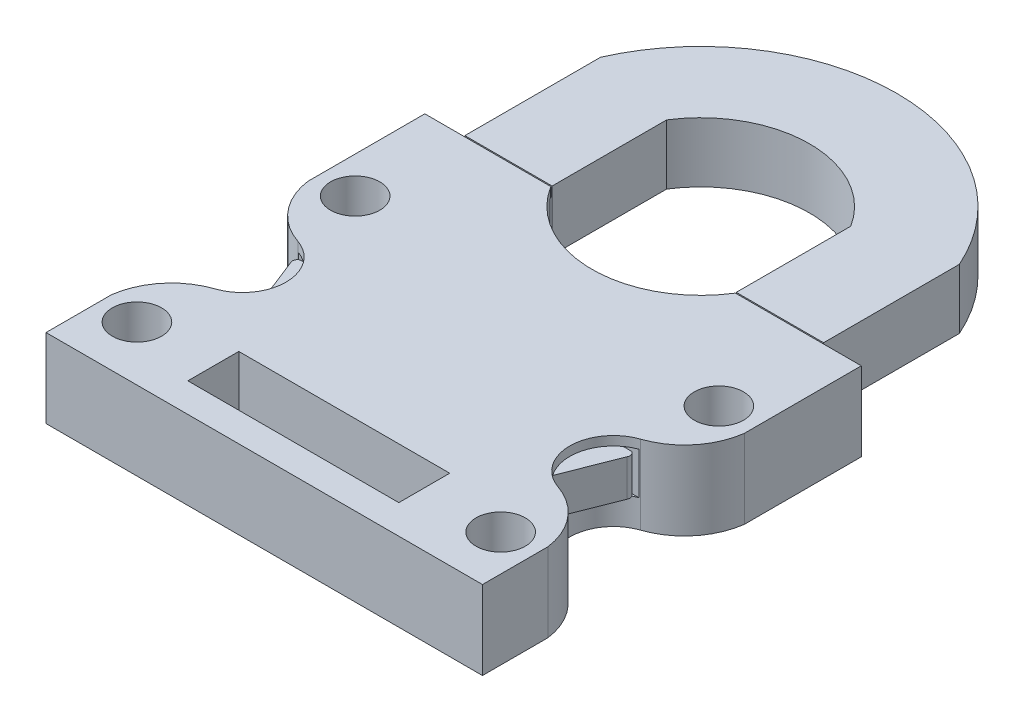
SolidWorks part; units mm, degrees
ref_plane "Front Plane" through (0, 0, 0) normal (0, 0, 1) x (1, 0, 0)
ref_plane "Top Plane" through (0, 0, 0) normal (0, 1, 0) x (1, 0, 0)
ref_plane "Right Plane" through (0, 0, 0) normal (1, 0, 0) x (0, 0, -1)
sketch "Sketch1" plane through (0, 0, 0) normal (0, 1, 0) x (1, 0, 0)
  line L0 (-38.1, -28.575) -> (38.1, -28.575)
  line L1 (31.75, -19.05) -> (-31.75, -19.05) construction
  line L2 (31.75, -19.05) -> (31.75, 19.05) construction
  line L3 (31.75, 19.05) -> (-31.75, 19.05) construction
  line L4 (-31.75, -19.05) -> (-31.75, 19.05) construction
  line L5 (31.75, -19.05) -> (-31.75, 19.05) construction
  line L6 (31.75, 19.05) -> (-31.75, -19.05) construction
  line L11 (38.1, -28.575) -> (38.1, 37.5615)
  line L13 (-38.1, 37.5615) -> (-38.1, -28.575)
  line L14 (-15.875, 37.5615) -> (-38.1, 37.5615)
  line L15 (0, -28.575) -> (0, 28.829) construction
  line L21 (15.875, 37.5615) -> (38.1, 37.5615)
  line L22 (0, 47.625) -> (0, -28.575) construction
  line L29 (0, 28.829) -> (0, -28.575) construction
  circle A0 centre (-31.75, 19.05) radius 2.75
  circle A1 centre (31.75, 19.05) radius 2.75
  circle A2 centre (31.75, -19.05) radius 2.75
  circle A3 centre (-31.75, -19.05) radius 2.75
  arc A4 (-15.875, 37.5615) -> (15.875, 37.5615) centre (0, 47.625) ccw
  point P0 (0, 0)
  point P10 (0, 0)
  dimension "D3" = 5.5
  dimension "D8" = 37.592
  dimension "D1" = 63.5
  dimension "D2" = 38.1
  dimension "D4" = 76.2
  dimension "D5" = 9.525
  dimension "D6" = 22.225
  dimension "D7" = 76.2
  dimension "D9" = 66.1365
extrude "Boss-Extrude1" add sketch "Sketch1" along normal blind 10.6045
sketch "Sketch2" plane through (0, 10.6045, 0) normal (0, 1, 0) x (1, 0, 0)
  circle A0 centre (-31.75, 19.05) radius 4.3
  circle A1 centre (31.75, 19.05) radius 4.3
  circle A2 centre (31.75, -19.05) radius 4.3
  circle A3 centre (-31.75, -19.05) radius 4.3
  dimension "D1" = 8.6
  dimension "D2" = 8.6
  dimension "D3" = 8.6
  dimension "D4" = 8.6
extrude "Cut-Extrude1" cut sketch "Sketch2" against normal blind 7
sketch "Sketch3" plane through (0, 0, -37.5615) normal (0, 0, -1) x (-1, 0, 0)
  line L0 (15.875, 0) -> (15.875, 5.3022) construction
  line L1 (15.875, 9.017) -> (25.4, 9.017)
  line L2 (15.875, 9.017) -> (15.875, 1.5875)
  line L3 (15.875, 1.5875) -> (25.4, 1.5875)
  line L4 (25.4, 9.017) -> (25.4, 1.5875)
  line L6 (15.875, 0) -> (38.1, 0) construction
  line L7 (15.875, 10.6045) -> (38.1, 10.6045) construction
  line L8 (38.1, 10.6045) -> (38.1, 0) construction
  line L9 (15.875, 10.6045) -> (15.875, 0) construction
  dimension "D2" = 1.5875
  dimension "D3" = 1.5875
  dimension "D4" = 12.7
extrude "Cut-Extrude2" cut sketch "Sketch3" against normal blind 30.5816
mirror "Mirror1" about plane through (0, 0, 0) normal (1, 0, 0) of "Cut-Extrude2"
sketch "Sketch4" plane through (-38.1, 0, 0) normal (-1, 0, 0) x (0, 0, 1)
  line L0 (-6.9799, 9.017) -> (-37.5615, 9.017) construction
  line L5 (-14.75, 7.1045) -> (14.75, 7.1045) construction
  line L6 (-14.75, 3.6045) -> (-14.75, 10.6045) construction
  line L7 (14.75, 10.6045) -> (14.75, 3.6045) construction
  line L9 (0, 0) -> (0, 10.6045) construction
  line L10 (-37.5615, 10.6045) -> (28.575, 10.6045) construction
  line L11 (7.13, 1.5875) -> (-7.13, 1.5875)
  line L12 (7.13, 1.5875) -> (7.13, 9.017)
  line L13 (7.13, 9.017) -> (-7.13, 9.017)
  line L14 (-7.13, 1.5875) -> (-7.13, 9.017)
  line L15 (7.13, 1.5875) -> (-7.13, 9.017) construction
  line L16 (7.13, 9.017) -> (-7.13, 1.5875) construction
  line L17 (-37.5615, 5.3022) -> (-7.13, 5.3022) construction
  line L18 (-37.5615, 10.6045) -> (-37.5615, 0) construction
  point P4 (0, 5.3022)
  dimension "D1" = 7.62
ref_plane "Plane1" through (0, 5.3022, 0) normal (0, 1, 0) x (1, 0, 0)
extrude "Cut-Extrude5" cut sketch "Sketch4" against normal up to body separate body
sketch "Sketch6" plane through (0, 5.3022, 0) normal (0, 1, 0) x (1, 0, 0)
  line L0 (15.875, 33.3699) -> (15.875, 7.13)
  line L1 (15.875, 7.13) -> (15.875, 37.5615) construction
  line L2 (15.875, 7.13) -> (9.525, 7.13)
  line L3 (15.875, 7.13) -> (-15.875, 7.13) construction
  line L4 (9.525, 7.13) -> (9.525, 28.5331)
  arc A2 (-18.0203, 36.2016) -> (18.0203, 36.2016) centre (0, 47.625) ccw
  arc A3 (9.525, 28.5331) -> (15.875, 33.3699) centre (0, 47.625) ccw
  dimension "D2" = 6.35
  dimension "D1" = 2.54
extrude "Cut-Extrude6" cut sketch "Sketch6" against normal mid plane 7.4295
mirror "Mirror3" about plane through (0, 0, 0) normal (1, 0, 0) of "Cut-Extrude6"
sketch "Sketch7" plane through (0, 5.3022, 0) normal (0, 1, 0) x (1, 0, 0)
  line L0 (-38.1, 17.145) -> (-38.1, 0)
  line L3 (-38.1, 37.5615) -> (-38.1, -28.575) construction
  line L4 (-24.765, 0) -> (-38.1, 0) construction
  line L6 (-38.1, 0) -> (-24.765, 0)
  arc A2 (-38.1, 17.145) -> (-29.9352, 7.2155) centre (-26.0155, 18.7602) ccw
  arc A3 (-29.9352, 7.2155) -> (-24.765, 0) centre (-32.385, 0) cw
  dimension "D1" = 12.192
  dimension "D3" = 7.62
  dimension "D2" = 13.335
  dimension "D4" = 17.145
extrude "Cut-Extrude7" cut sketch "Sketch7" against normal mid plane 11.43
mirror "Mirror4" about plane through (0, 0, 0) normal (1, 0, 0) of "Cut-Extrude7"
mirror "Mirror5" about plane through (0, 0, 0) normal (0, 0, 1) of "Mirror4", "Cut-Extrude7"
sketch "Sketch8" plane through (0, 5.3022, 0) normal (0, 1, 0) x (1, 0, 0)
  line L0 (0, -28.575) -> (0, 47.625) construction
  line L1 (-38.1, -28.575) -> (38.1, -28.575) construction
  line L2 (-15.875, 33.3699) -> (-15.875, 37.5615) construction
  line L3 (15.875, 33.3699) -> (15.875, 37.5615) construction
  line L4 (16.0734, 37.7599) -> (16.0734, 57.7459)
  line L5 (-16.0734, 37.7599) -> (-16.0734, 57.7459)
  line L6 (31.3134, 37.7599) -> (31.3134, 61.4621)
  line L7 (-31.3134, 37.7599) -> (-31.3134, 61.4621)
  line L8 (31.3134, 37.7599) -> (31.3134, 61.4621) construction
  line L9 (31.3134, 37.7599) -> (24.638, 37.7599)
  line L10 (24.638, 37.7599) -> (24.638, 6.622)
  line L11 (24.638, 6.622) -> (28.956, 6.622)
  line L12 (-24.638, 6.622) -> (-28.956, 6.622)
  line L13 (29.3613, 5.4184) -> (25.6836, -3.9348)
  line L14 (-29.3613, 5.4184) -> (-25.6836, -3.9348)
  line L15 (20.193, -2.8942) -> (20.193, 37.7599)
  line L16 (38.1, 37.5615) -> (15.875, 37.5615) construction
  line L17 (20.193, 37.7599) -> (16.0734, 37.7599)
  line L18 (25.4, 7.13) -> (25.4, 37.5615) construction
  line L19 (29.6966, 7.13) -> (25.4, 7.13) construction
  line L20 (-31.3134, 37.7599) -> (-24.638, 37.7599)
  line L21 (-20.193, 37.7599) -> (-16.0734, 37.7599)
  line L22 (-24.638, 37.7599) -> (-24.638, 6.622)
  line L23 (-20.193, -2.8942) -> (-20.193, 37.7599)
  line L28 (-31.3134, 37.7599) -> (-31.3134, 61.4621) construction
  circle A0 centre (0, 47.625) radius 18.796 construction
  arc A1 (16.0734, 57.7459) -> (-16.0734, 57.7459) centre (0, 47.625) ccw
  circle A2 centre (0, 47.625) radius 18.9944 construction
  arc A3 (31.3134, 61.4621) -> (-31.3134, 61.4621) centre (0, 47.625) ccw
  arc A4 (25.6836, -3.9348) -> (20.193, -2.8942) centre (23.0369, -2.8942) cw
  arc A5 (29.3613, 5.4184) -> (28.956, 6.622) centre (28.569, 5.8217) ccw
  arc A6 (-29.3613, 5.4184) -> (-28.956, 6.622) centre (-28.569, 5.8217) cw
  arc A7 (-25.6836, -3.9348) -> (-20.193, -2.8942) centre (-23.0369, -2.8942) ccw
  dimension "D2" = 37.592
  dimension "D15" = 0.889
  dimension "D13" = 9.3532
  dimension "D14" = 2.8439
  dimension "D1" = 76.2
  dimension "D4" = 0.1984
  dimension "D5" = 0.1984
  dimension "D7" = 0.1984
  dimension "D8" = 0.762
  dimension "D9" = 0.508
  dimension "D10" = 4.445
  dimension "D11" = 4.318
  dimension "D12" = 1.27
  dimension "D16" = 68.535
  dimension "D3" = 0.1984
  dimension "D6" = 15.24
extrude "Boss-Extrude3" add sketch "Sketch8" along normal blind 3.26 and the other way blind 3.16 separate body contours L6 A3 L7 L20 L14 L12 L21 L5 A1 L4 L17 L15 L11 L10 L9 region at (17.1503, 5.3022, -47.7529)
sketch "Sketch10" plane through (0, 10.6045, 0) normal (0, 1, 0) x (1, 0, 0)
  line L0 (-16.0734, 37.5615) -> (-16.0734, 37.5041)
  line L1 (-15.875, 37.5615) -> (-38.1, 37.5615) construction
  line L2 (-16.0734, 37.5615) -> (16.0734, 37.5615)
  line L4 (16.0734, 37.5615) -> (16.0734, 37.5041)
  arc A0 (-15.875, 37.5615) -> (15.875, 37.5615) centre (0, 47.625) ccw construction
  arc A1 (-15.875, 37.5615) -> (15.875, 37.5615) centre (0, 47.625) ccw construction
  arc A2 (-16.0426, 37.4553) -> (16.0426, 37.4553) centre (0, 47.625) ccw construction
  arc A3 (-16.0734, 37.5041) -> (16.0734, 37.5041) centre (0, 47.625) ccw
  dimension "D1" = 0.1984
extrude "Cut-Extrude8" cut sketch "Sketch10" against normal through all
sketch "Sketch11" plane through (0, 8.5623, 0) normal (0, 1, 0) x (1, 0, 0)
  line L0 (31.3134, 37.7599) -> (31.3134, 61.4621) construction
  line L1 (16.0734, 37.7599) -> (16.0734, 57.7459) construction
  line L2 (-16.0734, 37.7599) -> (-16.0734, 57.7459) construction
  line L3 (-31.3134, 37.7599) -> (-31.3134, 61.4621) construction
  line L4 (31.3134, 37.7599) -> (31.3134, 61.4621)
  line L5 (16.0734, 37.7599) -> (16.0734, 57.7459)
  line L6 (-16.0734, 37.7599) -> (-16.0734, 57.7459)
  line L7 (-31.3134, 37.7599) -> (-31.3134, 61.4621)
  line L8 (-31.3134, 37.7599) -> (-16.0734, 37.7599)
  line L9 (16.0734, 37.7599) -> (31.3134, 37.7599)
  arc A0 (31.3134, 61.4621) -> (-31.3134, 61.4621) centre (0, 47.625) ccw construction
  arc A1 (16.0734, 57.7459) -> (-16.0734, 57.7459) centre (0, 47.625) ccw construction
  arc A2 (31.3134, 61.4621) -> (-31.3134, 61.4621) centre (0, 47.625) ccw
  arc A3 (16.0734, 57.7459) -> (-16.0734, 57.7459) centre (0, 47.625) ccw
extrude "Boss-Extrude4" add sketch "Sketch11" along normal up to surface (2.0423 mm away) up to face at (0, 10.6045, -9.9519)
sketch "Sketch13" plane through (0, 10.6045, 0) normal (0, 1, 0) x (1, 0, 0)
  line L0 (-38.1, -28.575) -> (38.1, -28.575) construction
  line L1 (18.415, -23.495) -> (-18.415, -23.495)
  line L2 (18.415, -23.495) -> (18.415, -14.605)
  line L3 (18.415, -14.605) -> (-18.415, -14.605)
  line L4 (-18.415, -23.495) -> (-18.415, -14.605)
  line L5 (18.415, -23.495) -> (-18.415, -14.605) construction
  line L6 (18.415, -14.605) -> (-18.415, -23.495) construction
  point P0 (0, -19.05)
  dimension "D1" = 36.83
  dimension "D2" = 8.89
  dimension "D3" = 5.08
extrude "Cut-Extrude10" cut sketch "Sketch13" against normal through all
sketch "Sketch16" plane through (0, 0, -37.5615) normal (0, 0, -1) x (-1, 0, 0)
  line L0 (25.4, 9.017) -> (16.0734, 9.017) construction
  line L1 (25.4, 1.5875) -> (27.94, 1.5875)
  line L2 (25.4, 1.5875) -> (25.4, 9.017)
  line L3 (25.4, 9.017) -> (27.94, 9.017)
  line L4 (27.94, 1.5875) -> (27.94, 9.017)
  dimension "D1" = 2.54
extrude "Cut-Extrude11" cut sketch "Sketch16" against normal blind 12.7
mirror "Mirror6" about plane through (0, 0, 0) normal (1, 0, 0) of "Cut-Extrude11"
fillet "Fillet1" radius 10 2 edges at (25.4, 5.3022, -24.8615) (-25.4, 5.3022, -24.8615)
combine bodies "Combine1" operation type add bodies to combine 119 117
fillet "Fillet3" radius 1.27 4 edges at (20.193, 5.3523, -37.7599) (24.638, 5.3523, -37.7599) (-20.193, 5.3523, -37.7599) (-24.638, 5.3523, -37.7599)
sketch "Sketch17" plane through (0, 0, 0) normal (0, 1, 0) x (1, 0, 0)
  line L0 (18.415, -23.495) -> (18.415, -14.605) construction
  line L1 (-18.415, -23.495) -> (18.415, -23.495) construction
  line L2 (-18.415, -14.605) -> (-18.415, -23.495) construction
  line L3 (18.415, -14.605) -> (-18.415, -14.605) construction
  line L4 (38.1, -28.575) -> (38.1, -17.145) construction
  line L5 (-38.1, -28.575) -> (38.1, -28.575) construction
  line L6 (-38.1, -17.145) -> (-38.1, -28.575) construction
  line L7 (-38.1, 37.5615) -> (-38.1, 17.145) construction
  line L8 (38.1, 17.145) -> (38.1, 37.5615) construction
  line L9 (38.1, 37.5615) -> (16.0734, 37.5615) construction
  line L10 (-16.0734, 37.5615) -> (-38.1, 37.5615) construction
  line L11 (18.415, -23.495) -> (18.415, -14.605)
  line L12 (-18.415, -23.495) -> (18.415, -23.495)
  line L13 (-18.415, -14.605) -> (-18.415, -23.495)
  line L14 (18.415, -14.605) -> (-18.415, -14.605)
  line L15 (38.1, -28.575) -> (38.1, -17.145)
  line L16 (-38.1, -28.575) -> (38.1, -28.575)
  line L17 (-38.1, -17.145) -> (-38.1, -28.575)
  line L18 (-38.1, 37.5615) -> (-38.1, 17.145)
  line L19 (38.1, 17.145) -> (38.1, 37.5615)
  line L20 (38.1, 37.5615) -> (16.0734, 37.5615)
  line L21 (-16.0734, 37.5615) -> (-38.1, 37.5615)
  circle A0 centre (31.75, 19.05) radius 2.75 construction
  circle A1 centre (-31.75, 19.05) radius 2.75 construction
  circle A2 centre (-31.75, -19.05) radius 2.75 construction
  circle A3 centre (31.75, -19.05) radius 2.75 construction
  arc A4 (38.1, -17.145) -> (29.9352, -7.2155) centre (26.0155, -18.7602) ccw construction
  arc A5 (-29.9352, -7.2155) -> (-38.1, -17.145) centre (-26.0155, -18.7602) ccw construction
  arc A6 (-29.9352, -7.2155) -> (-29.9352, 7.2155) centre (-32.385, 0) ccw construction
  arc A7 (29.9352, 7.2155) -> (29.9352, -7.2155) centre (32.385, 0) ccw construction
  arc A8 (29.9352, 7.2155) -> (38.1, 17.145) centre (26.0155, 18.7602) ccw construction
  arc A9 (-38.1, 17.145) -> (-29.9352, 7.2155) centre (-26.0155, 18.7602) ccw construction
  arc A10 (-16.0734, 37.5041) -> (16.0734, 37.5041) centre (0, 47.625) ccw construction
  circle A11 centre (31.75, 19.05) radius 2.75
  circle A12 centre (-31.75, 19.05) radius 2.75
  circle A13 centre (-31.75, -19.05) radius 2.75
  circle A14 centre (31.75, -19.05) radius 2.75
  arc A15 (38.1, -17.145) -> (29.9352, -7.2155) centre (26.0155, -18.7602) ccw
  arc A16 (-29.9352, -7.2155) -> (-38.1, -17.145) centre (-26.0155, -18.7602) ccw
  arc A17 (-29.9352, -7.2155) -> (-29.9352, 7.2155) centre (-32.385, 0) ccw
  arc A18 (29.9352, 7.2155) -> (29.9352, -7.2155) centre (32.385, 0) ccw
  arc A19 (29.9352, 7.2155) -> (38.1, 17.145) centre (26.0155, 18.7602) ccw
  arc A20 (-38.1, 17.145) -> (-29.9352, 7.2155) centre (-26.0155, 18.7602) ccw
  arc A21 (-16.0734, 37.5041) -> (16.0734, 37.5041) centre (0, 47.625) ccw
ref_plane "Plane2" through (0, -3.16, 0) normal (0, 1, 0) x (1, 0, 0)
sketch "Sketch20" plane through (0, 1.5875, 0) normal (0, 1, 0) x (1, 0, 0)
  line L0 (18.415, -23.495) -> (18.415, -14.605) construction
  line L1 (-18.415, -23.495) -> (18.415, -23.495) construction
  line L2 (-18.415, -14.605) -> (-18.415, -23.495) construction
  line L3 (18.415, -14.605) -> (-18.415, -14.605) construction
  line L4 (18.415, -23.495) -> (18.415, -14.605)
  line L5 (-18.415, -23.495) -> (18.415, -23.495)
  line L6 (-18.415, -14.605) -> (-18.415, -23.495)
  line L7 (18.415, -14.605) -> (-18.415, -14.605)
  line L9 (16.0734, 37.5615) -> (16.0734, 37.5041)
  line L10 (-16.0734, 37.5041) -> (-16.0734, 37.5615)
  line L11 (-16.0734, 37.5615) -> (-38.1, 37.5615)
  line L12 (-38.1, 37.5615) -> (-38.1, 17.145)
  line L13 (-38.1, -17.145) -> (-38.1, -28.575)
  line L14 (-38.1, -28.575) -> (38.1, -28.575)
  line L15 (38.1, -28.575) -> (38.1, -17.145)
  line L16 (38.1, 17.145) -> (38.1, 37.5615)
  line L17 (38.1, 37.5615) -> (16.0734, 37.5615)
  line L18 (16.0734, 37.5615) -> (16.0734, 37.5041)
  line L19 (-16.0734, 37.5041) -> (-16.0734, 37.5615)
  line L20 (-16.0734, 37.5615) -> (-38.1, 37.5615)
  line L21 (-38.1, 37.5615) -> (-38.1, 17.145)
  line L22 (-38.1, -17.145) -> (-38.1, -28.575)
  line L23 (-38.1, -28.575) -> (38.1, -28.575)
  line L24 (38.1, -28.575) -> (38.1, -17.145)
  line L25 (38.1, 17.145) -> (38.1, 37.5615)
  line L26 (38.1, 37.5615) -> (16.0734, 37.5615)
  circle A0 centre (-31.75, 19.05) radius 2.75 construction
  circle A1 centre (-31.75, 19.05) radius 2.75
  circle A2 centre (31.75, 19.05) radius 2.75 construction
  circle A3 centre (31.75, 19.05) radius 2.75
  circle A4 centre (-31.75, -19.05) radius 2.75 construction
  circle A5 centre (-31.75, -19.05) radius 2.75
  circle A6 centre (31.75, -19.05) radius 2.75 construction
  arc A7 (-16.0734, 37.5041) -> (16.0734, 37.5041) centre (0, 47.625) ccw
  arc A8 (-38.1, 17.145) -> (-29.9352, 7.2155) centre (-26.0155, 18.7602) ccw
  arc A9 (-29.9352, -7.2155) -> (-29.9352, 7.2155) centre (-32.385, 0) ccw
  arc A10 (-29.9352, -7.2155) -> (-38.1, -17.145) centre (-26.0155, -18.7602) ccw
  arc A11 (38.1, -17.145) -> (29.9352, -7.2155) centre (26.0155, -18.7602) ccw
  arc A12 (29.9352, 7.2155) -> (29.9352, -7.2155) centre (32.385, 0) ccw
  arc A13 (29.9352, 7.2155) -> (38.1, 17.145) centre (26.0155, 18.7602) ccw
  arc A14 (-16.0734, 37.5041) -> (16.0734, 37.5041) centre (0, 47.625) ccw
  arc A15 (-38.1, 17.145) -> (-29.9352, 7.2155) centre (-26.0155, 18.7602) ccw
  arc A16 (-29.9352, -7.2155) -> (-29.9352, 7.2155) centre (-32.385, 0) ccw
  arc A17 (-29.9352, -7.2155) -> (-38.1, -17.145) centre (-26.0155, -18.7602) ccw
  arc A18 (38.1, -17.145) -> (29.9352, -7.2155) centre (26.0155, -18.7602) ccw
  arc A19 (29.9352, 7.2155) -> (29.9352, -7.2155) centre (32.385, 0) ccw
  arc A20 (29.9352, 7.2155) -> (38.1, 17.145) centre (26.0155, 18.7602) ccw
  circle A21 centre (31.75, -19.05) radius 2.75
  dimension "D1" = 0
extrude "Boss-Extrude5" add sketch "Sketch20" against normal up to surface and the other way blind 0.1 up to plane "Plane2"
sketch "Sketch21" plane through (0, 2.1423, 0) normal (0, -1, 0) x (1, 0, 0)
  line L0 (-31.3134, -37.7599) -> (-16.0734, -37.7599)
  line L1 (-16.0734, -37.7599) -> (-16.0734, -57.7459)
  line L2 (-31.3134, -37.7599) -> (-31.3134, -61.4621)
  line L3 (16.0734, -37.7599) -> (16.0734, -57.7459) construction
  line L4 (16.0734, -37.7599) -> (16.0734, -57.7459)
  line L5 (31.3134, -37.7599) -> (31.3134, -61.4621) construction
  line L6 (31.3134, -37.7599) -> (31.3134, -61.4621)
  line L7 (16.0734, -37.7599) -> (31.3134, -37.7599)
  arc A0 (-16.0734, -57.7459) -> (16.0734, -57.7459) centre (0, -47.625) ccw construction
  arc A1 (-16.0734, -57.7459) -> (16.0734, -57.7459) centre (0, -47.625) ccw
  arc A2 (-31.3134, -61.4621) -> (31.3134, -61.4621) centre (0, -47.625) ccw construction
  arc A3 (-31.3134, -61.4621) -> (31.3134, -61.4621) centre (0, -47.625) ccw
extrude "Boss-Extrude6" add sketch "Sketch21" along normal blind 2
